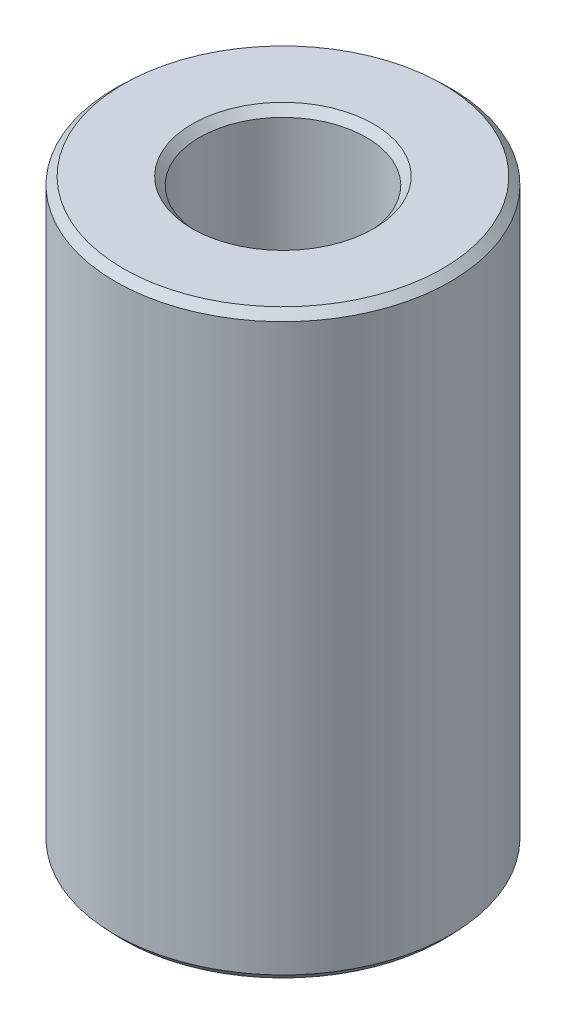
SolidWorks part; units mm, degrees
ref_plane "Front Plane" through (0, 0, 0) normal (0, 0, 1) x (1, 0, 0)
ref_plane "Top Plane" through (0, 0, 0) normal (0, 1, 0) x (1, 0, 0)
ref_plane "Right Plane" through (0, 0, 0) normal (1, 0, 0) x (0, 0, -1)
sketch "Sketch1" plane through (0, 0, 0) normal (0, 1, 0) x (1, 0, 0)
  circle A0 centre (0, 0) radius 5
  dimension "SLEEVE_OD" = 10
extrude "Boss-Extrude1" add sketch "Sketch1" along normal blind 17.3346
sketch "Sketch2" plane through (0, 0, 0) normal (0, 1, 0) x (1, 0, 0)
  circle A0 centre (0, 0) radius 2.4866
  dimension "BORE_D" = 4.9731
extrude "Cut-Extrude1" cut sketch "Sketch2" along normal through all
chamfer "Chamfer1" distance 0.2205 angle 46.727 4 edges at (0, 17.3346, 2.4866) (0, 0, 2.4866) (0, 0, 5) (0, 17.3346, 5) first distance on face at (0, 17.3346, 2.4866) first distance on face at (0, 0, 2.4866) first distance on face at (0, 17.3346, 5)
